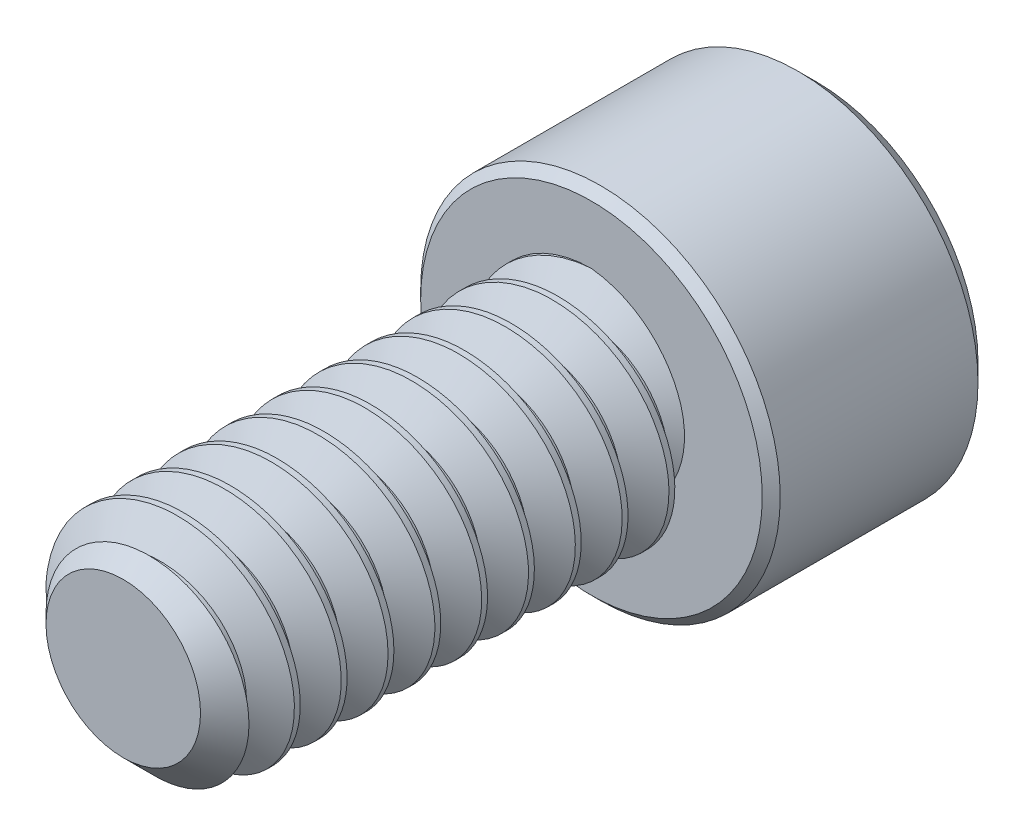
SolidWorks part; units mm, degrees
ref_plane "Front Plane" through (0, 0, 0) normal (0, 0, 1) x (1, 0, 0)
ref_plane "Top Plane" through (0, 0, 0) normal (0, 1, 0) x (1, 0, 0)
ref_plane "Right Plane" through (0, 0, 0) normal (1, 0, 0) x (0, 0, -1)
sketch "Sketch0" plane through (0, 0, 0) normal (1, 0, 0) x (0, 0, -1)
  line L0 (0, 0) -> (3.175, 0) construction
  point P2 (4.699, 0)
  point P4 (0, 0)
  dimension "D1" = 3.175
  dimension "D2" = 1.524
  dimension "Min Thread" = 0
sketch "Sketch1" plane through (0, 0, 0) normal (0, 0, 1) x (1, 0, 0)
  circle A0 centre (0, 0) radius 0.762
  dimension "OD" = 1.524
extrude "Extrude1" add sketch "Sketch1" against normal blind 3.175
sketch "Sketch2" plane through (0, 0, 0) normal (0, 0, 1) x (1, 0, 0)
  circle A0 centre (0, 0) radius 0.762 construction
  circle A1 centre (0, 0) radius 0.762
curve "Helix/Spiral1" pitch 0.3175 height 3.4925 radius 0.762 centre (0, 0, 0) axis (0, 0, -1) start towards (0, 1, 0) parameters "pitch"=0.3175
chamfer "Chamfer3" distance 0.2381 angle 45 1 edges at (0.762, 0, 0)
sketch "Sketch3" plane through (0, 0, 0) normal (1, 0, 0) x (0, 0, -1)
  line L0 (-0.2778, 0.762) -> (-0.1587, 0.5558)
  line L1 (-0.1587, 0.5558) -> (-0.1191, 0.5558)
  line L2 (-0.1191, 0.5558) -> (0, 0.762)
  line L3 (-0.2778, 0.762) -> (0, 0.762)
  line L4 (-0.1389, 0.762) -> (-0.1389, 0.5558) construction
  line L5 (-0.2183, 0.6589) -> (-0.0595, 0.6589) construction
  line L6 (0, 0.762) -> (0, -0.762) construction
  dimension "D1" = 0.0397
  dimension "D2" = 0.1588
  dimension "D3" = 60
sweep "Cut-Sweep1" cut profiles "Sketch3" path "Helix/Spiral1" align with end faces yes
sketch "Sketch5" plane through (0, 0, 0) normal (1, 0, 0) x (0, 0, -1)
  line L0 (3.175, -0.5618) -> (3.175, 0.5437) construction
  line L1 (3.175, 0.762) -> (0, 0.762)
  line L2 (3.175, 0.762) -> (3.175, 0)
  line L3 (3.175, 0) -> (-0.2773, 0)
  line L4 (0, 0) -> (3.175, 0) construction
  line L5 (0, 0.762) -> (-0.2773, 0)
  line L6 (0, 0) -> (5.715, 0) construction
  dimension "D1" = 70
  dimension "D3" = 2.54
revolve "partially thread" [suppressed] add sketch "Sketch5" angle 360 about L6
sketch "Sketch6" plane through (0, 0, -3.175) normal (0, 0, -1) x (-1, 0, 0)
  circle A0 centre (0, 0) radius 1.2192
  dimension "head dia" = 2.4384
extrude "Extrude2" add sketch "Sketch6" along normal blind 1.524
sketch "Sketch7" plane through (0, 0, -4.699) normal (0, 0, -1) x (-1, 0, 0)
  line L1 (0, 0.7332) -> (-0.635, 0.3666)
  line L2 (-0.635, 0.3666) -> (-0.635, -0.3666)
  line L3 (-0.635, -0.3666) -> (0, -0.7332)
  line L4 (0, -0.7332) -> (0.635, -0.3666)
  line L5 (0.635, -0.3666) -> (0.635, 0.3666)
  line L6 (0.635, 0.3666) -> (0, 0.7332)
  circle A0 centre (0, 0) radius 0.635 construction
  dimension "hex dia" = 1.27
extrude "Cut-Extrude1" cut sketch "Sketch7" against normal blind 0.9525
sketch "Sketch8" plane through (0, 0, -4.699) normal (0, 0, -1) x (-1, 0, 0)
  circle A0 centre (0, 0) radius 0.7332
extrude "Cut-Extrude2" cut sketch "Sketch8" against normal through all draft 45
chamfer "Chamfer1" distance 0.1219 angle 45 1 edges at (-1.2192, 0, -4.699)
chamfer "Chamfer2" distance 0.061 angle 45 1 edges at (-1.2192, 0, -3.175)
sketch "Sketch9" plane through (0, 0, 0) normal (1, 0, 0) x (0, 0, -1)
  line L0 (0, 0.762) -> (0, -0.762) construction
  line L1 (1.4287, 0.762) -> (1.4288, -0.762) construction
  line L2 (4.699, 1.2192) -> (4.699, -1.2192) construction
  line L3 (3.175, 1.2192) -> (3.175, -1.2192) construction
  line L4 (3.175, 1.1582) -> (3.175, -1.1582) construction
  line L5 (4.699, -1.0973) -> (4.699, 1.0973) construction
  line L6 (3.175, -1.2192) -> (3.175, 1.2192) construction
  line L7 (0, 0.5239) -> (0, -0.5239) construction
  line L8 (-0.2778, 0.762) -> (0, 0.762) construction
  line L9 (1.4287, 0) -> (0, 0) construction
  dimension "D1" = 1.4287
equation "\"D3@Helix/Spiral1\" = \"screw length@Extrude1\"+\"pitch@Helix/Spiral1\""
equation "\"D1@Sketch3\" = \"pitch@Helix/Spiral1\"*.125"
equation "\"D2@Sketch3\" = \"pitch@Helix/Spiral1\"*.5"
equation "\"D1@Cut-Extrude1\" = \"hex dia@Sketch7\"*.75"
equation "\"D1@Chamfer1\" = \"head dia@Sketch6\"*.05"
equation "\"D1@Sketch9\" = \"pitch@Helix/Spiral1\"*4.50"
equation "\"D1@Chamfer2\" = \"D1@Chamfer1\"/2"
equation "\"D1@Chamfer3\" = \"pitch@Helix/Spiral1\"*.750"
equation "\"D1@Sketch0\" = \"screw length@Extrude1\""
equation "\"D2@Sketch0\" = \"head depth@Extrude2\""
